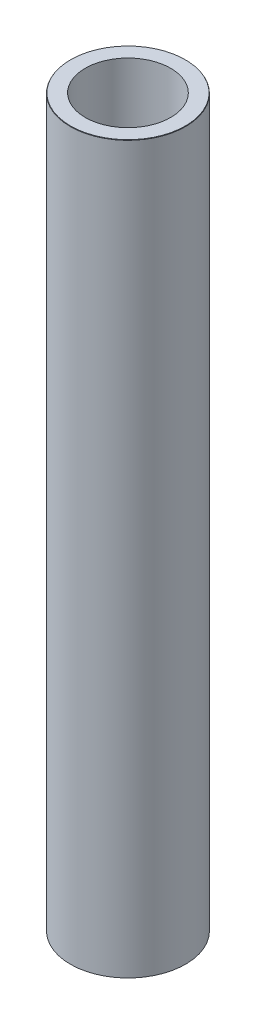
SolidWorks part; units mm, degrees
ref_plane "Front Plane" through (0, 0, 0) normal (0, 0, 1) x (1, 0, 0)
ref_plane "Top Plane" through (0, 0, 0) normal (0, 1, 0) x (1, 0, 0)
ref_plane "Right Plane" through (0, 0, 0) normal (1, 0, 0) x (0, 0, -1)
sketch "Sketch1" plane through (0, 0, 0) normal (0, 1, 0) x (1, 0, 0)
  circle A0 centre (0, 0) radius 32.5
  dimension "SHAFT_OD" = 65
extrude "Boss-Extrude1" add sketch "Sketch1" along normal blind 409.5304
sketch "Sketch2" plane through (0, 0, 0) normal (0, 1, 0) x (1, 0, 0)
  circle A0 centre (0, 0) radius 24.0855
  dimension "BORE_D" = 48.171
extrude "Cut-Extrude1" cut sketch "Sketch2" along normal through all
chamfer "Chamfer1" distance 0.2287 angle 30 2 edges at (0, 409.5304, 32.5) (0, 0, 32.5) first distance on face at (0, 409.5304, 32.5) first distance on face at (0, 0, 24.0855)
